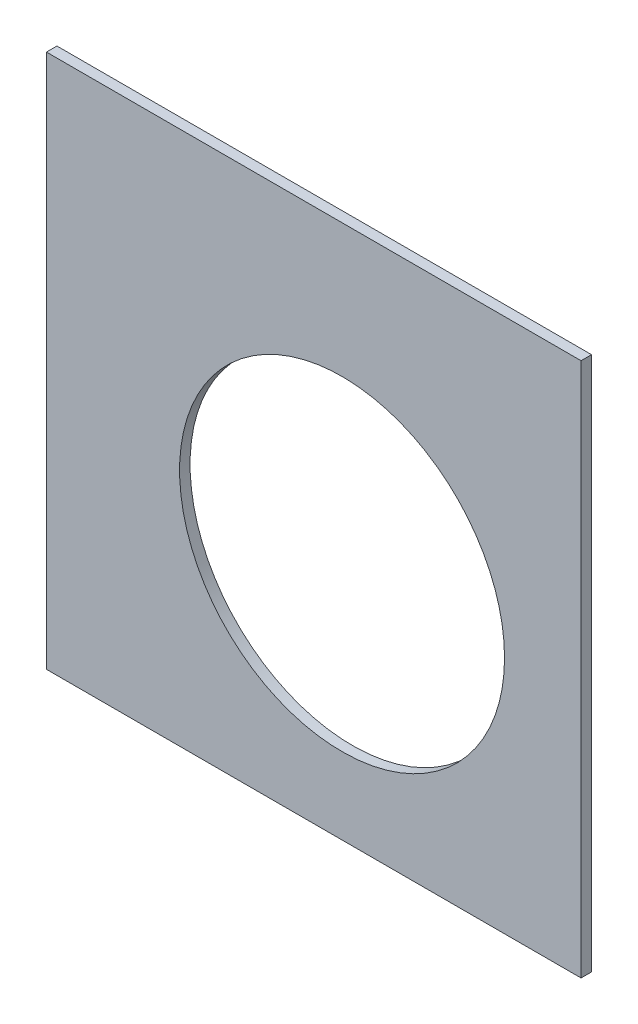
SolidWorks part; units mm, degrees
ref_plane "Front Plane" through (0, 0, 0) normal (0, 0, 1) x (1, 0, 0)
ref_plane "Top Plane" through (0, 0, 0) normal (0, 1, 0) x (1, 0, 0)
ref_plane "Right Plane" through (0, 0, 0) normal (1, 0, 0) x (0, 0, -1)
sketch "Sketch1" plane through (0, 0, 0) normal (0, 0, 1) x (1, 0, 0)
  line L1 (0, 0) -> (323.85, 0)
  line L2 (0, 0) -> (0, 323.85)
  line L4 (323.85, 0) -> (323.85, 323.85)
  line L5 (0, 323.85) -> (323.85, 323.85)
  circle A0 centre (179.07, 144.78) radius 98.425
  dimension "D3" = 196.85
  dimension "D1" = 179.07
  dimension "D2" = 179.07
  dimension "D7" = 323.85
extrude "Boss-Extrude1" add sketch "Sketch1" along normal blind 6.35
